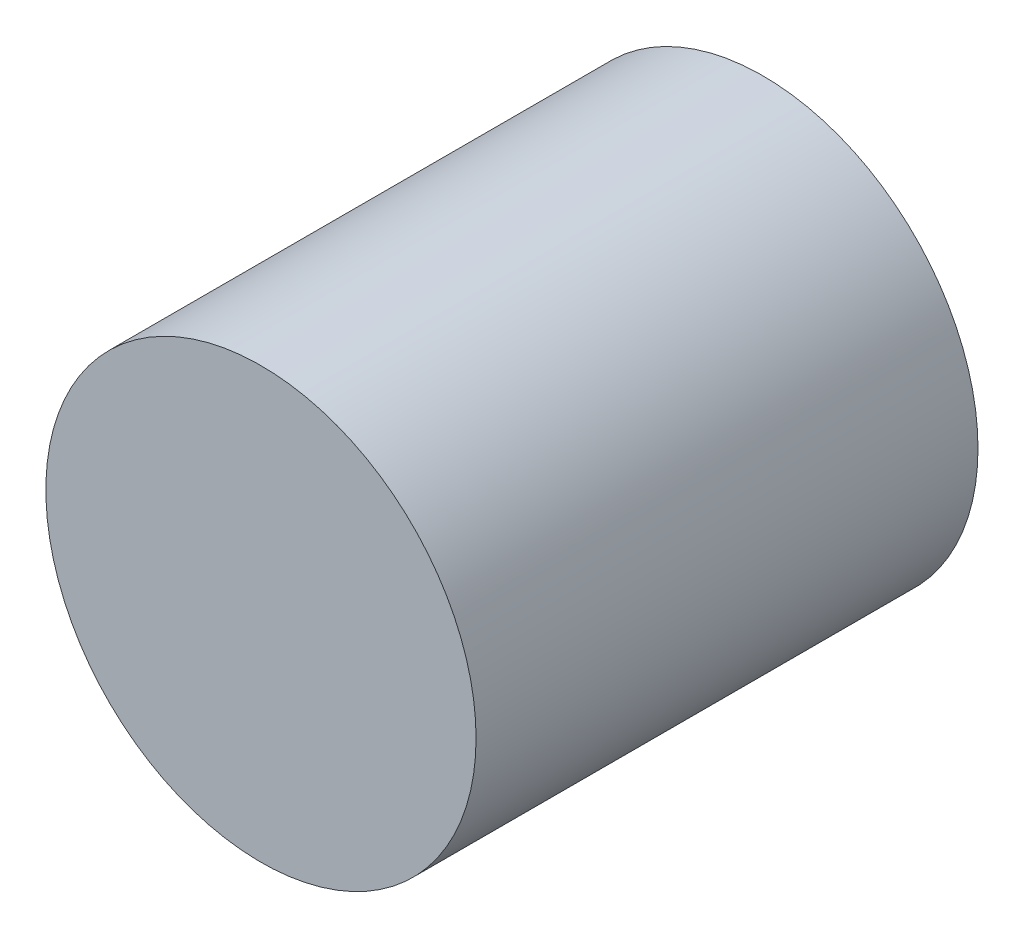
SolidWorks part; units mm, degrees
ref_plane "Спереди" through (0, 0, 0) normal (0, 0, 1) x (1, 0, 0)
ref_plane "Сверху" through (0, 0, 0) normal (0, 1, 0) x (1, 0, 0)
ref_plane "Справа" through (0, 0, 0) normal (1, 0, 0) x (0, 0, -1)
sketch "основа" plane through (0, 0, 0) normal (0, 0, 1) x (1, 0, 0)
  line L1 (-7.6, 7.6) -> (7.6, 7.6)
  line L2 (-7.6, 7.6) -> (-7.6, -7.6)
  line L3 (-7.6, -7.6) -> (7.6, -7.6)
  line L4 (7.6, 7.6) -> (7.6, -7.6)
  line L5 (-7.6, 7.6) -> (7.6, -7.6) construction
  line L6 (-7.6, -7.6) -> (7.6, 7.6) construction
  circle A0 centre (0, 0) radius 15
  point P0 (0, 0)
  point P6 (0, 0)
  dimension "D5" = 30
  dimension "D1" = 15.2
  dimension "D2" = 15.2
extrude "Бобышка-основа" add sketch "основа" along normal blind 35 contours A0
extrude "Вырез под профиль" cut sketch "основа<4>" along normal blind 30 contours L4 L1 L2 L3 region at (0, 0, 0)
sketch "основа<4>" plane through (0, 0, 0) normal (0, 0, 1) x (1, 0, 0) same geometry as "основа"
